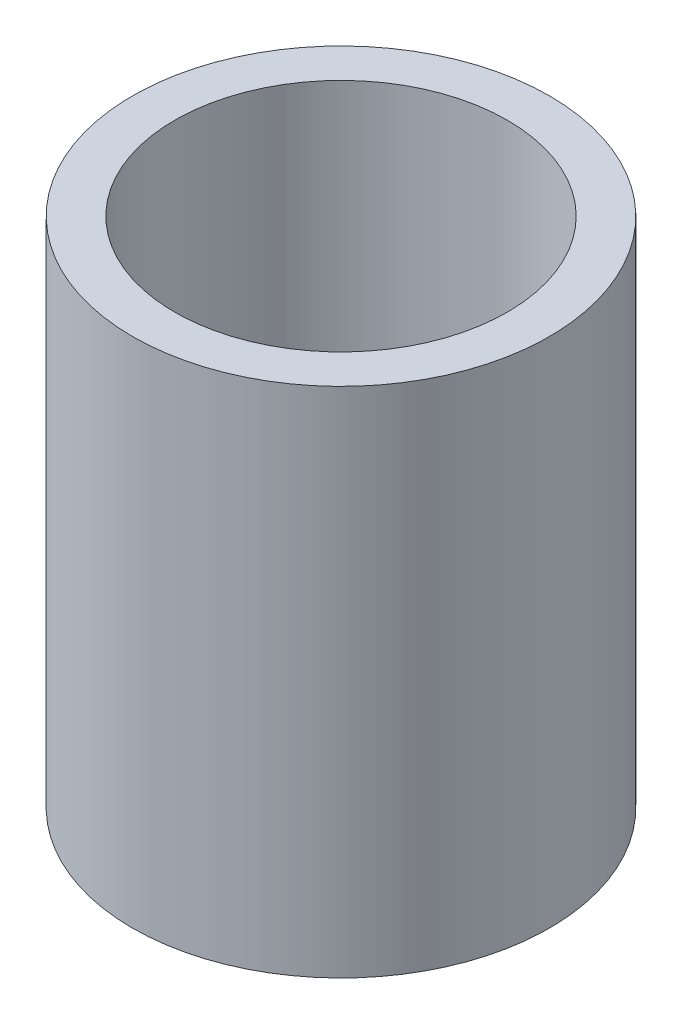
SolidWorks part; units mm, degrees
ref_plane "Front Plane" through (0, 0, 0) normal (0, 0, 1) x (1, 0, 0)
ref_plane "Top Plane" through (0, 0, 0) normal (0, 1, 0) x (1, 0, 0)
ref_plane "Right Plane" through (0, 0, 0) normal (1, 0, 0) x (0, 0, -1)
sketch "Sketch1" plane through (0, 0, 0) normal (0, 1, 0) x (1, 0, 0)
  circle A0 centre (0, 0) radius 32.5
  dimension "SLEEVE_OD" = 65
extrude "Boss-Extrude1" add sketch "Sketch1" along normal blind 79.8807
sketch "Sketch2" plane through (0, 0, 0) normal (0, 1, 0) x (1, 0, 0)
  circle A0 centre (0, 0) radius 25.9281
  dimension "BORE_D" = 51.8563
extrude "Cut-Extrude1" cut sketch "Sketch2" along normal through all
chamfer "Chamfer1" distance 3.8996 angle 45 rebuild error yes
